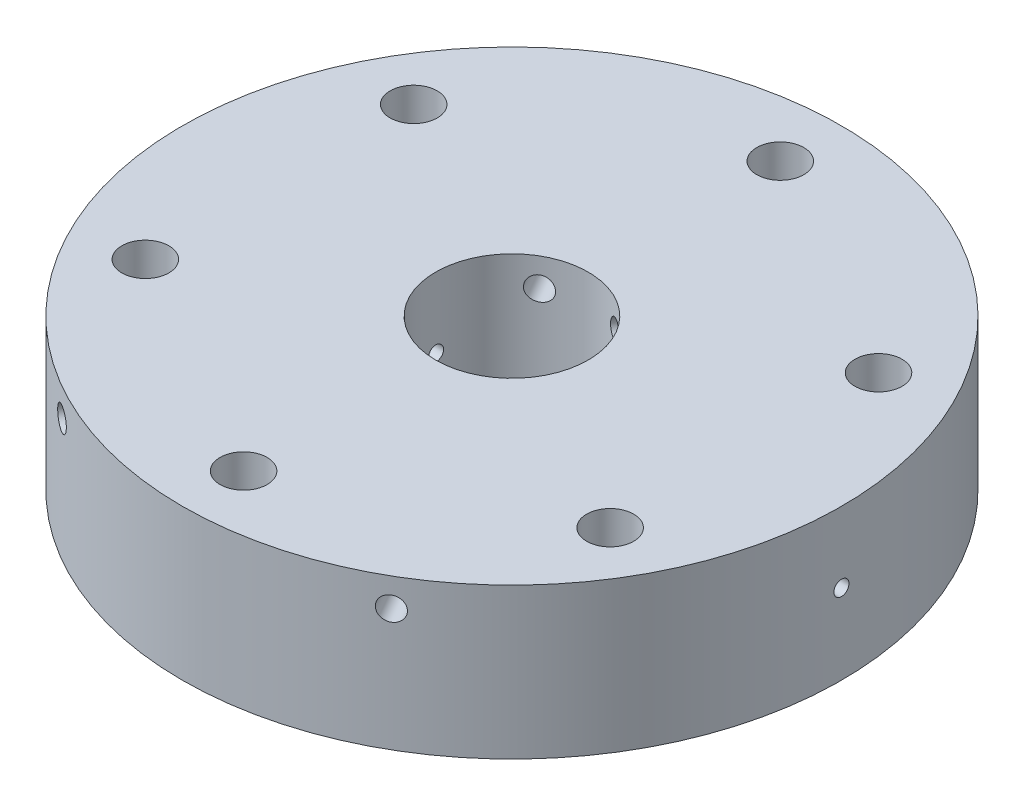
SolidWorks part; units mm, degrees
ref_plane "Front Plane" through (0, 0, 0) normal (0, 0, 1) x (1, 0, 0)
ref_plane "Top Plane" through (0, 0, 0) normal (0, 1, 0) x (1, 0, 0)
ref_plane "Right Plane" through (0, 0, 0) normal (1, 0, 0) x (0, 0, -1)
sketch "Sketch1" plane through (0, 0, 0) normal (0, 1, 0) x (1, 0, 0)
  circle A0 centre (0, 0) radius 88.9
  dimension "D1" = 177.8
extrude "Boss-Extrude1" add sketch "Sketch1" along normal blind 40.64 contours A0
sketch "Sketch2" plane through (0, 40.64, 0) normal (0, 1, 0) x (1, 0, 0)
  circle A0 centre (0, 0) radius 20.574
  dimension "D1" = 41.148
extrude "Cut-Extrude1" cut sketch "Sketch2" against normal through all
sketch "Sketch3" plane through (0, 0, 0) normal (1, 0, 0) x (0, 0, -1)
  line L0 (0, 0) -> (0, 21.59) construction
  line L2 (-88.9, 0) -> (88.9, 0) construction
  circle A0 centre (0, 21.59) radius 2.032
  dimension "D1" = 4.064
  dimension "D2" = 21.59
extrude "Cut-Extrude4" cut sketch "Sketch3" against normal through all both and the other way through all
sketch "Sketch5" plane through (0, 0, 0) normal (1, 0, 0) x (0, 0, -1)
  line L0 (0, 0) -> (0, 50000) construction
  line L1 (0, 0) -> (50000, 0) construction
  line L2 (-20.574, 0) -> (20.574, 0) construction
  point P7 (0, 0)
ref_plane "Plane2" through (0, 0, 0) normal (0.5, 0, -0.866) x (0, 1, 0)
sketch "Sketch6" plane through (0, 0, 0) normal (0.5, 0, -0.866) x (0, 1, 0)
  line L2 (-200000, 0) -> (250000, 0) construction
  line L3 (40.64, -88.9) -> (40.64, 88.9) construction
  circle A1 centre (33.02, 0) radius 3.175
  dimension "D1" = 6.35
  dimension "D2" = 7.62
extrude "Cut-Extrude5" cut sketch "Sketch6" against normal through all both and the other way through all
mirror "Mirror1" about plane through (0, 0, 0) normal (0, 0, 1) of "Cut-Extrude5"
sketch "Sketch7" plane through (0, 0, 0) normal (0, -1, 0) x (1, 0, 0)
  line L0 (0, 0) -> (0, 50000) construction
  circle A0 centre (0, 0) radius 72.39 construction
  dimension "D1" = 144.78
hole_wizard "1/2 (0.5) Diameter Hole1" positions "3DSketch1" profile "Sketch8" hole size "1/2" standard "ANSI Inch" end condition through all
sketch3d "3DSketch1"
  line L0 (0, 0, 0) -> (0, 0, 50000) construction
  circle A0 centre (0, 0, 0) radius 72.39 construction
  point P0 (0, 0, 72.39)
  point P6 (0, -72.39, 0)
sketch "Sketch8" plane through (0, 0, 72.39) normal (1, 0, 0) x (0, 0, -1)
  line L0 (0, 0) -> (0, 40.64)
  line L1 (0, 40.64) -> (6.35, 40.64)
  line L2 (6.35, 40.64) -> (6.35, 0.635)
  line L3 (6.35, 0.635) -> (6.985, 0)
  line L5 (6.985, 0) -> (0, 0)
  line L6 (-6.35, 0.635) -> (-6.985, 0) construction
  line L11 (0, -6.35) -> (0, 107.95) construction
  dimension "Thru Hole Dia." = 12.7
  dimension "Thru Hole Depth" = 40.64
  dimension "Near C'Sink Dia." = 13.97
  dimension "Near C'Sink Angle" = 90
pattern_circular "CirPattern1" count 6 over 360 about axis through (0, 0, 0) along (0, 1, 0) of "1/2 (0.5) Diameter Hole1"
sketch "Sketch9" plane through (0, 0, 0) normal (0, 0, 1) x (1, 0, 0)
  line L0 (-72.39, 0) -> (72.39, 0) construction
  line L1 (45.72, 0) -> (55.88, 0)
  line L2 (45.72, 0) -> (45.72, 5.08)
  line L3 (45.72, 5.08) -> (55.88, 5.08)
  line L4 (55.88, 0) -> (55.88, 5.08)
  point P6 (50.8, 0)
  dimension "D1" = 10.16
  dimension "D2" = 5.08
  dimension "D3" = 50.8
revolve "Cut-Revolve1" cut sketch "Sketch9" angle 360 about axis through (0, 40.64, 0) along (0, -1, 0)
equation "\"D2@Sketch9\"=\"D1@Sketch9\"/2"
